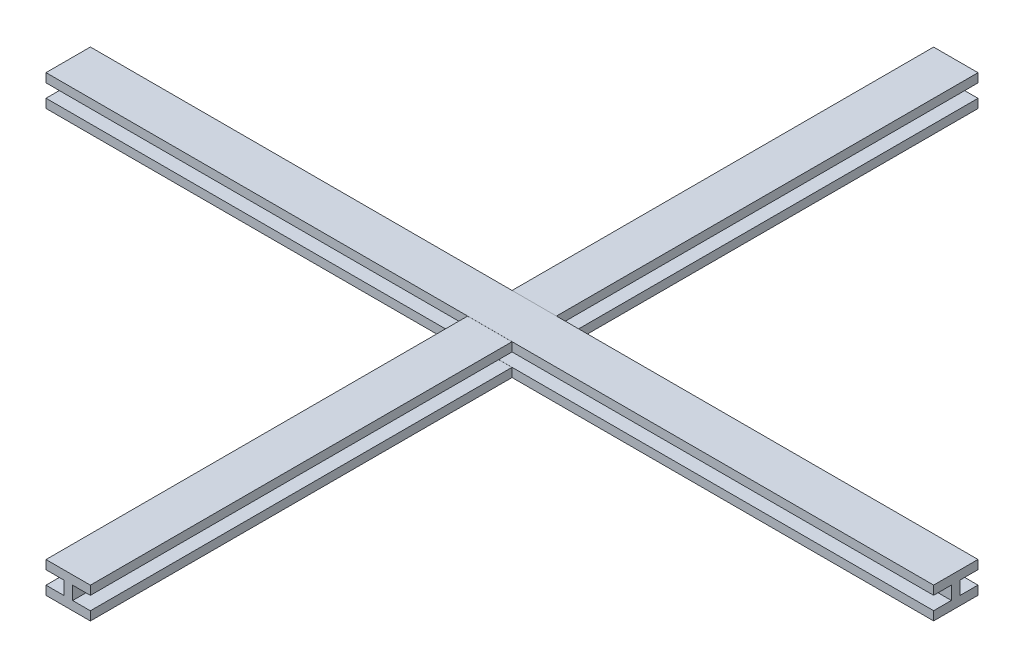
SolidWorks part; units mm, degrees
ref_plane "Front Plane" through (0, 0, 0) normal (0, 0, 1) x (1, 0, 0)
ref_plane "Top Plane" through (0, 0, 0) normal (0, 1, 0) x (1, 0, 0)
ref_plane "Right Plane" through (0, 0, 0) normal (1, 0, 0) x (0, 0, -1)
sketch "Sketch1" plane through (0, 0, 0) normal (0, 0, 1) x (1, 0, 0)
  line L0 (10, 15) -> (50, 15)
  line L4 (10, 15) -> (10, -15)
  line L5 (0, 0) -> (0, 43.0764) construction
  line L7 (-50, 35) -> (50, 35)
  line L8 (-50, 35) -> (-50, 15)
  line L9 (-50, 15) -> (-10, 15)
  line L10 (50, 35) -> (50, 15)
  line L13 (50, -35) -> (50, -15)
  line L14 (-50, -35) -> (50, -35)
  line L15 (-50, -35) -> (-50, -15)
  line L16 (-50, -15) -> (-10, -15)
  line L17 (10, -15) -> (50, -15)
  line L19 (-10, 15) -> (-10, -15)
  point P0 (0, 0)
  point P6 (0, 25)
  dimension "D1" = 40
  dimension "D2" = 20
  dimension "D3" = 100
  dimension "D4" = 40
  dimension "D5" = 20
  dimension "D6" = 30
  dimension "D7" = 30
  dimension "D9" = 20
  dimension "D10" = 100
  dimension "D11" = 40
  dimension "D12" = 40
  dimension "D13" = 10
  dimension "D14" = 15
  dimension "D15" = 50
  dimension "D16" = 35
extrude "Boss-Extrude1" add sketch "Sketch1" along normal blind 1000 and the other way blind 1000
sketch "Sketch2" plane through (0, 0, 0) normal (1, 0, 0) x (0, 0, -1)
  line L0 (10, 15.1498) -> (50, 15.1498)
  line L1 (10, 15.1498) -> (10, -14.8502)
  line L2 (-50, 35.1498) -> (50, 35.1498)
  line L3 (-50, 35.1498) -> (-50, 15.1498)
  line L4 (-50, 15.1498) -> (-10, 15.1498)
  line L5 (50, 35.1498) -> (50, 15.1498)
  line L6 (50, -34.8502) -> (50, -14.8502)
  line L7 (-50, -34.8502) -> (50, -34.8502)
  line L8 (-50, -34.8502) -> (-50, -14.8502)
  line L9 (-50, -14.8502) -> (-10, -14.8502)
  line L10 (10, -14.8502) -> (50, -14.8502)
  line L11 (-10, 15.1498) -> (-10, -14.8502)
  point P0 (0, 0.1498)
  point P2 (-3.4605, 27.0975)
  dimension "D1" = 20
  dimension "D2" = 100
  dimension "D3" = 40
  dimension "D4" = 40
  dimension "D5" = 20
  dimension "D6" = 30
  dimension "D7" = 30
  dimension "D8" = 20
  dimension "D9" = 100
  dimension "D10" = 40
  dimension "D11" = 40
  dimension "D12" = 10
  dimension "D13" = 15
  dimension "D14" = 50
  dimension "D15" = 35
extrude "Boss-Extrude2" add sketch "Sketch2" along normal blind 1000 and the other way blind 1000
